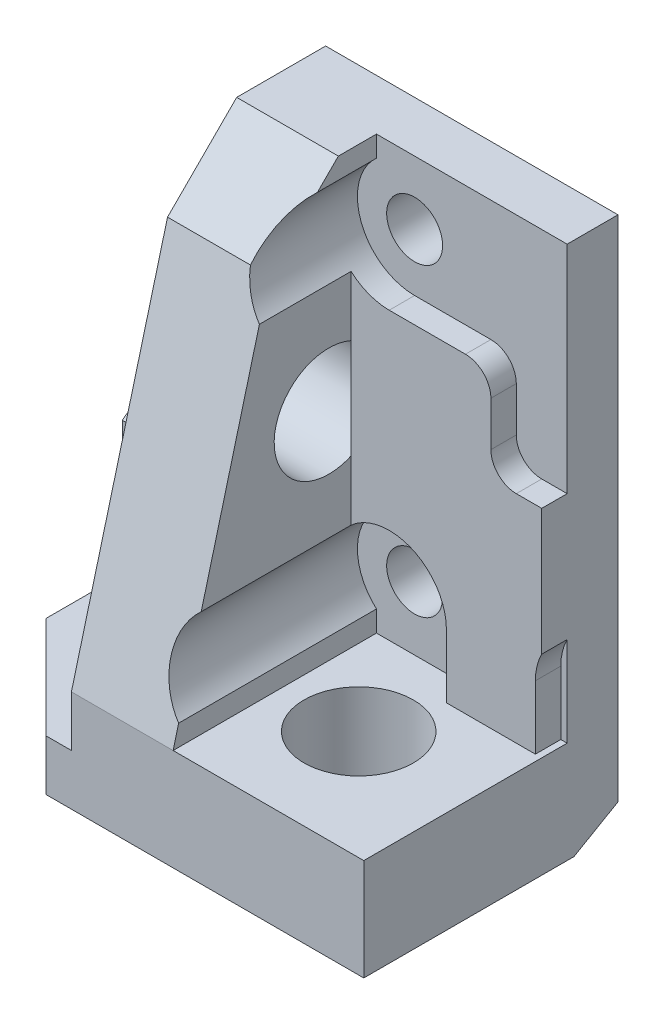
SolidWorks part; units mm, degrees
ref_plane "前视基准面" through (0, 0, 0) normal (0, 0, 1) x (1, 0, 0)
ref_plane "上视基准面" through (0, 0, 0) normal (0, 1, 0) x (1, 0, 0)
ref_plane "右视基准面" through (0, 0, 0) normal (1, 0, 0) x (0, 0, -1)
sketch "草图1" plane through (0, 0, 0) normal (0, 0, 1) x (1, 0, 0)
  line L0 (0, 0) -> (8, 0) construction
  line L1 (8, 0) -> (8, 12) construction
  line L2 (8, 12) -> (0, 12) construction
  line L3 (0, 12) -> (0, 0) construction
  line L4 (0, 6) -> (8, 6) construction
  line L5 (-7.5, 14.5) -> (15.5, 14.5)
  line L6 (-7.5, 14.5) -> (-7.5, -2.5)
  line L7 (-7.5, -2.5) -> (15.5, -2.5)
  line L8 (15.5, 14.5) -> (15.5, -2.5)
  line L9 (4, 12) -> (4, 14.5) construction
  circle A0 centre (0, 0) radius 1.1
  circle A1 centre (8, 0) radius 1.1
  circle A2 centre (0, 12) radius 1.1
  circle A3 centre (8, 12) radius 1.1
  dimension "D1" = 2.2
  dimension "D2" = 12
  dimension "D3" = 8
  dimension "D4" = 17
  dimension "D5" = 23
extrude "凸台-拉伸1" add sketch "草图1" along normal blind 3
sketch "草图2" plane through (-7.5, 0, 0) normal (-1, 0, 0) x (0, 0, 1)
  line L0 (5.5, 14.5) -> (10, -2.5)
  line L1 (0, 14.5) -> (5.5, 14.5)
  line L2 (0, 14.5) -> (0, -2.5)
  line L3 (0, -2.5) -> (5.5, -2.5)
  line L4 (5.5, 14.5) -> (5.5, -2.5) construction
  line L5 (10, -2.5) -> (5.5, -2.5)
  dimension "D1" = 5.5
  dimension "D2" = 4.5
extrude "凸台-拉伸2" add sketch "草图2" against normal blind 6
sketch "草图3" plane through (0, 0, 3) normal (0, 0, 1) x (1, 0, 0)
  circle A0 centre (0, 12) radius 2.25
  circle A1 centre (8, 12) radius 2.25
  circle A2 centre (0, 12) radius 1.1 construction
  circle A3 centre (0, 0) radius 2.25
  circle A4 centre (8, 0) radius 2.25
  dimension "D1" = 4.5
extrude "切除-拉伸1" cut sketch "草图3" against normal blind 1 and the other way through all
sketch "草图4" plane through (0, 0, 3) normal (0, 0, 1) x (1, 0, 0)
  line L0 (15.5, 14.5) -> (-1.5, 14.5) construction
  line L1 (11, 14.5) -> (15.5, 14.5)
  line L2 (11, 14.5) -> (11, -2.5)
  line L3 (11, -2.5) -> (15.5, -2.5)
  line L4 (15.5, 14.5) -> (15.5, -2.5)
  dimension "D1" = 4.5
extrude "切除-拉伸2" cut sketch "草图4" against normal up to next
sketch "草图5" plane through (-7.5, 0, 0) normal (-1, 0, 0) x (0, 0, 1)
  line L4 (0, 14.5) -> (0, -2.5)
  line L5 (0, -2.5) -> (10, -2.5)
  line L6 (10, -2.5) -> (5.5, 14.5)
  line L7 (5.5, 14.5) -> (0, 14.5)
  line L8 (0, 14.5) -> (0, -2.5)
  line L9 (0, -2.5) -> (10, -2.5)
  line L11 (5.5, 14.5) -> (0, 14.5)
  line L12 (10, -2.5) -> (5.5, 14.5)
  dimension "D1" = 0
extrude "切除-拉伸3" cut sketch "草图5" against normal blind 2
sketch "草图6" plane through (-5.5, 0, 0) normal (-1, 0, 0) x (0, 0, 1)
  line L0 (2.75, 14.5) -> (5, -2.5) construction
  line L1 (5.5, 14.5) -> (0, 14.5) construction
  line L2 (0, -2.5) -> (10, -2.5) construction
  circle A1 centre (3.875, 6) radius 2.15
  dimension "D2" = 4.3
extrude "切除-拉伸4" cut sketch "草图6" against normal blind 4
sketch "草图7" plane through (0, -2.5, 0) normal (0, -1, 0) x (1, 0, 0)
  line L1 (-5.5, 10) -> (11, 10)
  line L2 (-5.5, 10) -> (-5.5, 0)
  line L3 (-5.5, 0) -> (11, 0)
  line L4 (11, 10) -> (11, 0)
extrude "凸台-拉伸3" add sketch "草图7" along normal blind 4
sketch "草图8" plane through (0, -6.5, 0) normal (0, -1, 0) x (1, 0, 0)
  line L0 (-5.5, 5.7) -> (11, 5.7) construction
  line L1 (-5.5, 10) -> (-5.5, 0) construction
  line L2 (11, 0) -> (11, 10) construction
  line L3 (-5.5, 0) -> (11, 0) construction
  circle A0 centre (1.5, 5.7) radius 2.15
  dimension "D2" = 4.3
  dimension "D3" = 7
  dimension "D1" = 5.7
extrude "切除-拉伸5" cut sketch "草图8" against normal up to surface (4 mm away) up to face at (4.75, -2.5, 6.5)
chamfer "倒角1" distance 1 angle 60 1 edges at (2.75, -6.5, 0) first distance on face at (1.1, 0, 0)
chamfer "倒角2" distance 4 angle 45 1 edges at (11, -4.5, 10)
sketch "草图9" plane through (0, 0, 3) normal (0, 0, 1) x (1, 0, 0)
  line L0 (-1.5, 13.6771) -> (-1.5, 14.5)
  line L1 (-1.5, 14.5) -> (2.25, 14.5)
  line L2 (11, 14.5) -> (-1.5, 14.5) construction
  line L3 (2.25, 14.5) -> (2.25, 12)
  line L4 (5.75, 12) -> (5.75, 14.5)
  line L5 (5.75, 14.5) -> (11, 14.5)
  line L6 (11, 14.5) -> (11, 9.75)
  line L7 (11, 14.5) -> (11, -2.5) construction
  line L8 (11, 9.75) -> (8, 9.75)
  line L9 (2.25, 0) -> (2.25, -2.5)
  line L10 (7, -2.5) -> (-1.5, -2.5) construction
  line L11 (2.25, -2.5) -> (-1.5, -2.5)
  line L12 (-1.5, -2.5) -> (-1.5, -1.6771)
  line L13 (5.75, 0) -> (5.75, -2.5)
  line L14 (-1.5, -2.5) -> (11, -2.5) construction
  line L15 (5.75, -2.5) -> (11, -2.5)
  line L16 (11, -2.5) -> (11, 2.25)
  line L17 (11, 2.25) -> (8, 2.25)
  arc A0 (-1.5, 10.3229) -> (-1.5, 13.6771) centre (0, 12) ccw construction
  circle A1 centre (8, 12) radius 2.25 construction
  circle A2 centre (8, 12) radius 2.25 construction
  arc A3 (2.25, 12) -> (-1.5, 13.6771) centre (0, 12) ccw
  arc A4 (8, 9.75) -> (5.75, 12) centre (8, 12) ccw
  arc A5 (-1.5, -1.6771) -> (-1.5, 1.6771) centre (0, 0) ccw construction
  circle A6 centre (8, 0) radius 2.25 construction
  circle A7 centre (8, 0) radius 2.25 construction
  arc A8 (5.75, 0) -> (8, 2.25) centre (8, 0) ccw
  arc A9 (-1.5, -1.6771) -> (2.25, 0) centre (0, 0) ccw
extrude "切除-拉伸6" cut sketch "草图9" against normal up to surface (1 mm away) up to face at (1.1, 12, 2)
fillet "圆角1" radius 2 1 edges at (11, 14.5, 1)
sketch "草图10" plane through (0, 0, 2) normal (0, 0, 1) x (1, 0, 0)
  line L0 (5.75, 14.5) -> (2.25, 14.5) construction
  line L1 (4, 14.5) -> (11, 14.5)
  line L2 (4, 9.75) -> (4, 6)
  line L3 (4, 6) -> (11, 6)
  line L4 (11, 14.5) -> (11, 6)
  line L5 (11, 9.75) -> (11, 2.25) construction
  line L6 (0, 9.75) -> (4, 9.75)
  line L7 (2.25, 14.5) -> (2.25, 12) construction
  line L8 (2.25, 14.5) -> (4, 14.5)
  line L9 (2.25, 14.5) -> (2.25, 12)
  arc A0 (-1.5, 13.6771) -> (2.25, 12) centre (0, 12) ccw construction
  arc A1 (-1.5, 10.3229) -> (2.25, 12) centre (0, 12) ccw construction
  arc A2 (0, 9.75) -> (2.25, 12) centre (0, 12) ccw
extrude "切除-拉伸7" cut sketch "草图10" along normal up to next
fillet "圆角2" radius 1 2 edges at (4, 6, 2.5) (4, 9.75, 2.5)
chamfer "倒角3" distance 2 angle 45 1 edges at (-3.5, 14.5, 5.5) first distance on face at (0.6667, 14.5, 2.5)
sketch "草图11" plane through (0, -6.5, 0) normal (0, -1, 0) x (1, 0, 0)
  line L0 (7, 10) -> (-5.5, 10) construction
  line L1 (6, 10) -> (11, 10)
  line L2 (6, 10) -> (6, 0)
  line L3 (6, 0) -> (11, 0)
  line L4 (11, 10) -> (11, 0)
  dimension "D1" = 5
extrude "切除-拉伸8" cut sketch "草图11" against normal up to next
sketch "草图12" plane through (-5.5, 0, 0) normal (-1, 0, 0) x (0, 0, 1)
  line L0 (0, -5.5) -> (1.7321, -6.5)
  line L1 (1.7321, -6.5) -> (3, -6.5)
  line L5 (3, 1.5) -> (0, 1.5)
  line L6 (0, 1.5) -> (0, -5.5)
  line L7 (3, -6.5) -> (3, 1.5)
  dimension "D1" = 8
  dimension "D2" = 3
extrude "凸台-拉伸4" add sketch "草图12" along normal blind 5
sketch "草图13" plane through (0, 0, 3) normal (0, 0, 1) x (1, 0, 0)
  circle A0 centre (-8, 0) radius 1.1
  circle A1 centre (0, 0) radius 1.1 construction
  dimension "D1" = 8
extrude "切除-拉伸9" cut sketch "草图13" against normal up to next
sketch "草图14" plane through (0, 0, 3) normal (0, 0, 1) x (1, 0, 0)
  circle A0 centre (-8, 0) radius 2.25
  arc A1 (2.25, 0) -> (-1.5, -1.6771) centre (0, 0) ccw construction
extrude "切除-拉伸10" cut sketch "草图14" against normal up to surface (1 mm away) up to face at (1.1, 0, 2)
sketch "草图16" plane through (-10.5, 0, 0) normal (-1, 0, 0) x (0, 0, 1)
  line L0 (2, 1.5) -> (0, 3)
  line L1 (3, 1.5) -> (0, 1.5) construction
  line L2 (0, 3) -> (0, 1.5)
  line L4 (0, 1.5) -> (2, 1.5)
  dimension "D1" = 1.5
  dimension "D2" = 2
extrude "凸台-拉伸6" add sketch "草图16" against normal up to surface (5 mm away) up to face at (-5.5, 3.535, 4.465)
fillet "圆角3" radius 2 1 edges at (-10.5, 1.5, 2.5)
sketch "草图15" plane through (0, 0, 3) normal (0, 0, 1) x (1, 0, 0)
  line L0 (-5.5, -6.5) -> (-5.5, -2.5) construction
  line L1 (-10.5, -6.5) -> (-5.5, -6.5)
  line L2 (-10.5, -6.5) -> (-10.5, -4.5)
  line L3 (-10.5, -4.5) -> (-5.5, -4.5)
  line L4 (-5.5, -6.5) -> (-5.5, -4.5)
  dimension "D1" = 2
extrude "凸台-拉伸5" add sketch "草图15" along normal up to surface (7 mm away) up to face at (-0.1, -4.1, 10)
sketch "草图17" plane through (-10.5, 0, 0) normal (-1, 0, 0) x (0, 0, 1)
  line L0 (2, 1.5) -> (3, 0.75)
  line L1 (3, -4.5) -> (3, 1.5) construction
  line L2 (3, 0.75) -> (2, 1.5) construction
  line L3 (3, 0.75) -> (3, 1.5)
  line L4 (3, 1.5) -> (2, 1.5)
extrude "切除-拉伸11" cut sketch "草图17" against normal up to surface (5 mm away) up to face at (-5.5, 3.85, 3.875)
chamfer "倒角4" distance 4 angle 45 1 edges at (-10.5, -5.5, 10)
